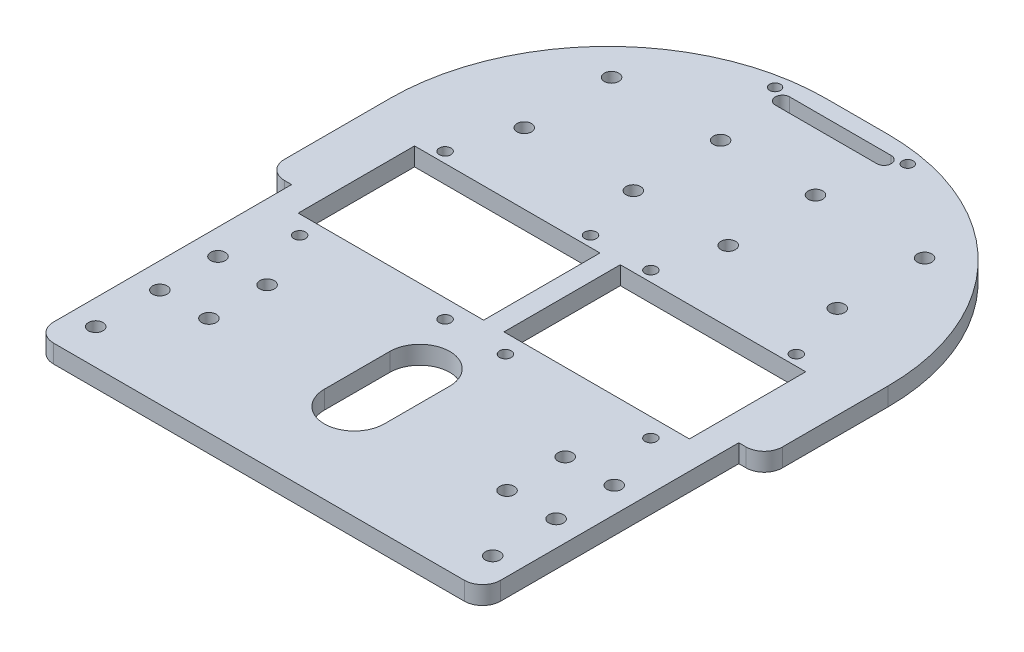
SolidWorks part; units mm, degrees
ref_plane "Front Plane" through (0, 0, 0) normal (0, 0, 1) x (1, 0, 0)
ref_plane "Top Plane" through (0, 0, 0) normal (0, 1, 0) x (1, 0, 0)
ref_plane "Right Plane" through (0, 0, 0) normal (1, 0, 0) x (0, 0, -1)
sketch "Sketch1" plane through (0, 0, 0) normal (0, 1, 0) x (1, 0, 0)
  line L0 (0, 90.99) -> (0, -94.01) construction
  line L1 (-94.5795, 0) -> (90.4205, 0) construction
  line L2 (-68.5, 80) -> (-68.5, -84.5)
  line L3 (-68.5, -84.5) -> (68.5, -84.5)
  line L4 (68.5, -84.5) -> (68.5, 80)
  line L5 (68.5, 80) -> (-68.5, 80)
  line L6 (-68.5, -14) -> (-68.5, -90)
  line L7 (-68.5, -90) -> (-61.5, -90)
  line L8 (-61.5, -90) -> (-61.5, -14)
  line L9 (-61.5, -14) -> (-68.5, -14)
  line L10 (61.5, -90) -> (61.5, -14)
  line L11 (68.5, -90) -> (61.5, -90)
  line L12 (68.5, -14) -> (68.5, -90)
  line L13 (61.5, -14) -> (68.5, -14)
  dimension "D1" = 61.5
  dimension "D2" = 68.5
  dimension "D3" = 80
  dimension "D4" = 185
  dimension "D5" = 185
  dimension "D6" = 84.5
  dimension "D7" = 76
  dimension "D8" = 94
  dimension "D9" = 68.5
extrude "Boss-Extrude2" add sketch "Sketch1" along normal blind 5 contours L10 L13 L4 L5 L2 L9 L8 L7 L3 L11 region at (0, 0, 0.0973)
fillet "Fillet8" radius 60 2 edges at (68.5, 2.5, -80) (-68.5, 2.5, -80)
sketch "Sketch4" plane through (0, 5, 0) normal (0, 1, 0) x (1, 0, 0)
  line L0 (0, 0) -> (0, 80) construction
  line L1 (0, 80) -> (0, -84.5) construction
  line L2 (0, -40.25) -> (0, -58.25) construction
  line L3 (-68.5, 3) -> (68.5, 3) construction
  line L4 (-68.5, 20) -> (-68.5, -14) construction
  line L5 (68.5, -14) -> (68.5, 20) construction
  line L6 (-61.5, -84.5) -> (-61.5, -14) construction
  line L7 (8.5, 80) -> (-8.5, 80) construction
  line L8 (-61.5, -84.5) -> (61.5, -84.5) construction
  line L9 (61.5, -84.5) -> (61.5, -14) construction
  line L10 (-61.5, -49.25) -> (61.5, -49.25) construction
  line L13 (8.2559, -40.25) -> (8.2559, -58.25)
  line L16 (-8.2559, -40.25) -> (-8.2559, -58.25)
  line L17 (-53.7989, 12.1126) -> (-2.7989, 12.1126)
  line L18 (-2.7989, 12.1126) -> (-53.7989, 12.1126) construction
  line L19 (-53.7989, 12.1126) -> (-53.7989, -19.8874) construction
  line L20 (-2.7989, 12.1126) -> (-2.7989, -19.8874)
  line L21 (-2.7989, -19.8874) -> (-53.7989, -19.8874)
  line L22 (-53.7989, -19.8874) -> (-53.7989, 12.1126)
  line L23 (2.7989, -19.8874) -> (53.7989, -19.8874)
  line L24 (2.7989, 12.1126) -> (2.7989, -19.8874)
  line L25 (53.7989, 12.1126) -> (2.7989, 12.1126)
  line L26 (53.7989, -19.8874) -> (53.7989, 12.1126)
  line L27 (-13.9003, 73.4227) -> (14.0397, 73.4227) construction
  line L28 (-13.9003, 72.4027) -> (-13.9003, 74.4427) construction
  line L29 (14.0397, 72.4027) -> (14.0397, 74.4427) construction
  line L30 (-13.9003, 75.39) -> (14.0397, 75.39)
  line L31 (-13.9003, 71.4554) -> (14.0397, 71.4554)
  line L32 (-61.5, -84.5) -> (-61.5, -14) construction
  line L33 (-61.5, -84.5) -> (61.5, -84.5) construction
  circle A2 centre (-41, -41.25) radius 2
  circle A10 centre (41, -41.25) radius 2
  circle A13 centre (41, -57.25) radius 2
  circle A14 centre (-41, -57.25) radius 2
  circle A15 centre (-54.5, -41.25) radius 2
  circle A16 centre (-54.5, -57.25) radius 2
  circle A17 centre (54.5, -57.25) radius 2
  circle A18 centre (54.5, -41.25) radius 2
  arc A23 (8.2559, -40.25) -> (-8.2559, -40.25) centre (0, -40.25) ccw
  arc A24 (-8.2559, -58.25) -> (8.2559, -58.25) centre (0, -58.25) ccw
  circle A25 centre (-48.2989, 15.0126) radius 1.605
  circle A26 centre (-8.2989, 15.0126) radius 1.605
  circle A27 centre (-48.2989, -24.9874) radius 1.605
  circle A28 centre (-8.2989, -24.9874) radius 1.605
  circle A29 centre (48.2989, -24.9874) radius 1.605
  circle A30 centre (8.2989, -24.9874) radius 1.605
  circle A31 centre (8.2989, 15.0126) radius 1.605
  circle A32 centre (48.2989, 15.0126) radius 1.605
  circle A37 centre (13.0471, 55.5443) radius 2
  circle A38 centre (43.0471, 55.5443) radius 2
  circle A39 centre (43.0471, 31.5443) radius 2
  circle A40 centre (13.0471, 31.5443) radius 2
  circle A41 centre (-43.0471, 55.5443) radius 2
  circle A42 centre (-43.0471, 31.5443) radius 2
  circle A43 centre (-13.0471, 31.5443) radius 2
  circle A44 centre (-13.0471, 55.5443) radius 2
  circle A46 centre (-18.1803, 75.6527) radius 1.5
  circle A47 centre (18.3197, 75.6527) radius 1.5
  arc A48 (-13.9003, 75.39) -> (-13.9003, 71.4554) centre (-13.9003, 73.4227) ccw
  arc A49 (14.0397, 71.4554) -> (14.0397, 75.39) centre (14.0397, 73.4227) ccw
  circle A51 centre (-54.599, -74.7963) radius 2
  circle A52 centre (54.599, -74.7963) radius 2
  point P50 (0, -49.25)
  point P110 (0.0697, 73.4227)
  dimension "D2" = 4
  dimension "D13" = 4
  dimension "D10" = 7
  dimension "D11" = 8.2559
  dimension "D5" = 3.21
  dimension "D6" = 4
  dimension "D7" = 3
  dimension "D3" = 16
  dimension "D4" = 16
  dimension "D8" = 3.9345
  dimension "D9" = 13.5
  dimension "D12" = 18
  dimension "D14" = 6.901
  dimension "D15" = 9.7037
extrude "Cut-Extrude1" cut sketch "Sketch4" against normal blind 5
fillet "Fillet17" radius 5 4 edges at (68.5, 2.5, 14) (61.5, 2.5, 84.5) (-61.5, 2.5, 84.5) (-68.5, 2.5, 14)
ref_plane "Plane1" through (61.5, 5, 14) normal (0, 0, -1) x (-1, 0, 0)
